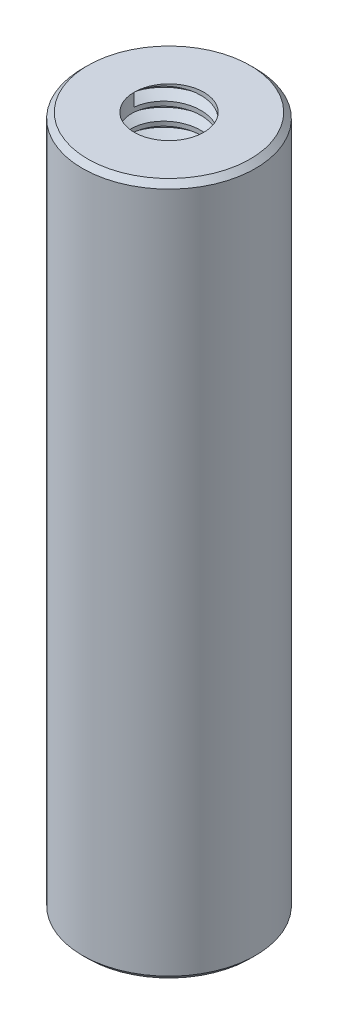
SolidWorks part; units mm, degrees
material "6061-T6 (SS)"
ref_plane "Alzado" through (0, 0, 0) normal (0, 0, 1) x (1, 0, 0)
ref_plane "Planta" through (0, 0, 0) normal (0, 1, 0) x (1, 0, 0)
ref_plane "Vista lateral" through (0, 0, 0) normal (1, 0, 0) x (0, 0, -1)
sketch "Croquis2" plane through (0, 0, 0) normal (0, 1, 0) x (1, 0, 0)
  circle A0 centre (0, 0) radius 6.35
  dimension "D1" = 12.7
extrude "Saliente-Extruir1" add sketch "Croquis2" along normal mid plane 50.8
chamfer "Chaflán1" distance 0.3969 angle 45 2 edges at (0, -25.4, 6.35) (0, 25.4, 6.35)
sketch "Croquis3" plane through (0, 0, 0) normal (0, 1, 0) x (1, 0, 0)
  circle A0 centre (0, 0) radius 2.5527
  dimension "D1" = 5.1054
extrude "Tap Hole 1" cut sketch "Croquis3" against normal blind 19.05 from surface starting at face at (0, 25.4, 5.9531)
extrude "Tap Hole 2" cut sketch "Croquis3<2>" along normal blind 19.05 from surface starting at face at (0, -25.4, 5.9531)
sketch "Croquis3<2>" plane through (0, 0, 0) normal (0, 1, 0) x (1, 0, 0) same geometry as "Croquis3"
sketch "Croquis4" plane through (0, 0, 0) normal (0, 1, 0) x (1, 0, 0)
  circle A0 centre (0, 0) radius 3.2639
  dimension "D1" = 6.5278
extrude "Clearance Hole" [suppressed] cut sketch "Croquis4" against normal through all both and the other way through all
thread "Rosca1" pitch 1.27 method cut profile "Perfil de rosca1" start angle 0, offset 0, length 0, pitch 1.27, diameter 5.1054
ref_plane "Plano1" through (-2.5527, 25.4, 0) normal (0, 0, 1) x (-1, 0, 0)
sketch "Perfil de rosca1" plane through (-2.5527, 25.4, 0) normal (0, 0, 1) x (-1, 0, 0)
  line L0 (0, 0) -> (0, 1.27) construction
  line L1 (0, 0) -> (0.6874, 0.3969)
  line L2 (0.6874, 0.3969) -> (0.6874, 0.5556)
  line L3 (0.6874, 0.5556) -> (0, 0.9525)
  line L4 (0.6874, 0.4762) -> (0, 0.4762) construction
  line L11 (0, 0) -> (0, 0.9525)
  point P2 (0, 0)
  dimension "Pitch" = 1.27
  dimension "Profile_Angle" = 60
  dimension "Profile_Land" = 0.1588
  dimension "Profile_Height" = 0.6874
thread "Rosca2" pitch 1.27 method cut profile "Perfil de rosca2" start angle 0, offset 0, length 0, pitch 1.27, diameter 5.1054
ref_plane "Plano2" through (2.5527, -25.4, 0) normal (0, 0, 1) x (1, 0, 0)
sketch "Perfil de rosca2" plane through (2.5527, -25.4, 0) normal (0, 0, 1) x (1, 0, 0)
  line L0 (0, 0) -> (0, 1.27) construction
  line L1 (0, 0) -> (0.6874, 0.3969)
  line L2 (0.6874, 0.3969) -> (0.6874, 0.5556)
  line L3 (0.6874, 0.5556) -> (0, 0.9525)
  line L4 (0.6874, 0.4762) -> (0, 0.4762) construction
  line L11 (0, 0) -> (0, 0.9525)
  point P2 (0, 0)
  dimension "Pitch" = 1.27
  dimension "Profile_Angle" = 60
  dimension "Profile_Land" = 0.1588
  dimension "Profile_Height" = 0.6874
equation "\"OD\"= 0.5pulgadas"
equation "\"Largo\"= 2pulgadas"
equation "\"Tap Hole\"= IIF ( \"OD\" = 0.375pulgadas , 0.1590pulgadas , 0.201pulgadas )"
equation "\"Spacer Hole\"= IIF ( \"OD\" = 0.375pulgadas , 0.196pulgadas , 0.257pulgadas )"
equation "\"D1@Croquis2\"=\"OD\""
equation "\"D1@Saliente-Extruir1\"=\"Largo\""
equation "\"D1@Croquis3\"=\"Tap Hole\""
equation "\"D1@Croquis4\"=\"Spacer Hole\""
